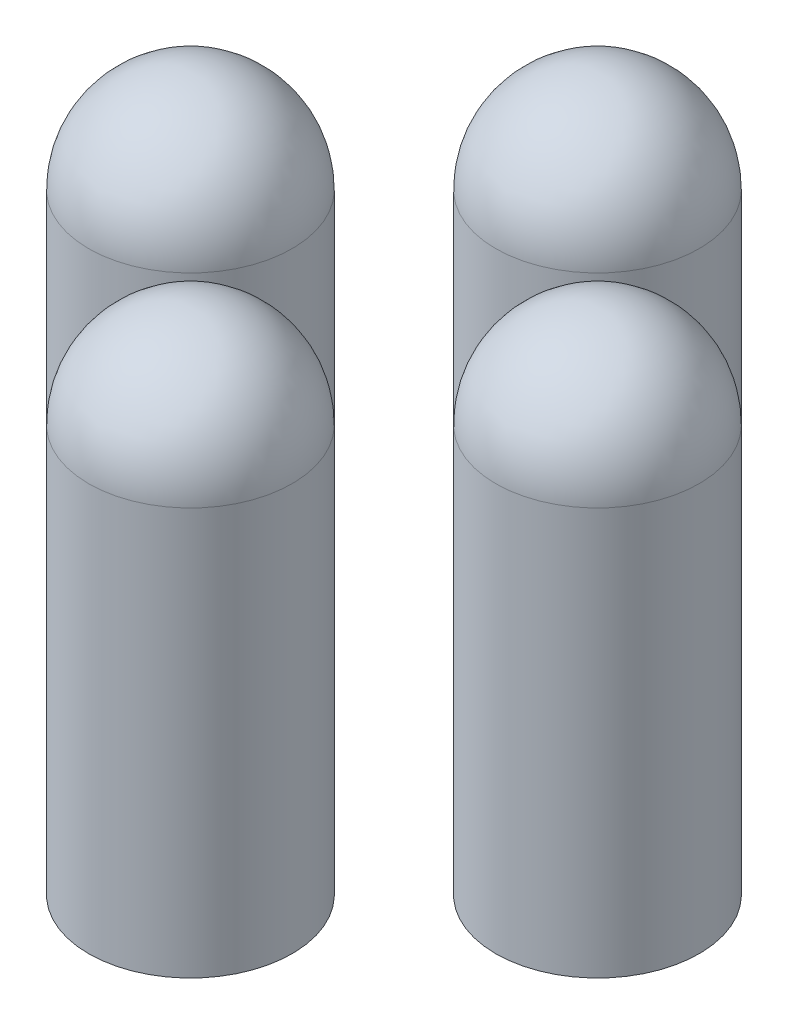
SolidWorks part; units mm, degrees
ref_plane "Front Plane" through (0, 0, 0) normal (0, 0, 1) x (1, 0, 0)
ref_plane "Top Plane" through (0, 0, 0) normal (0, 1, 0) x (1, 0, 0)
ref_plane "Right Plane" through (0, 0, 0) normal (1, 0, 0) x (0, 0, -1)
sketch "Sketch1" plane through (0, 0, 0) normal (0, 1, 0) x (1, 0, 0)
  circle A0 centre (0, 0) radius 5
  circle A1 centre (10, 10) radius 5
  circle A2 centre (20, 0) radius 5
  circle A3 centre (10, -10) radius 5
  point P12 (10, 0)
  dimension "D1" = 4
extrude "Boss-Extrude1" add sketch "Sketch1" along normal blind 20
dome "Dome4" faces to dome 1 distance 5 reverse direction no elliptical dome no face at (0, 20, 5) parameters "D1"=5
dome "Dome5" faces to dome 1 distance 5 reverse direction no elliptical dome no face at (10, 20, -5) parameters "D1"=5
dome "Dome6" faces to dome 1 distance 5 reverse direction no elliptical dome no face at (20, 20, 5) parameters "D1"=5
dome "Dome7" faces to dome 1 distance 5 reverse direction no elliptical dome no face at (10, 20, 15) parameters "D1"=5
